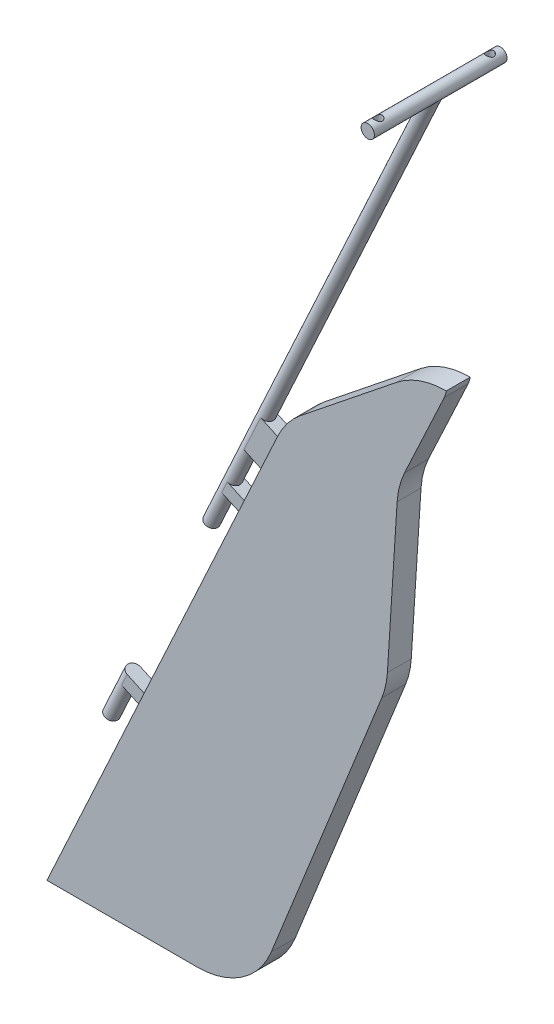
SolidWorks part; units mm, degrees
ref_plane "Plan de face" through (0, 0, 0) normal (0, 0, 1) x (1, 0, 0)
ref_plane "Plan de dessus" through (0, 0, 0) normal (0, 1, 0) x (1, 0, 0)
ref_plane "Plan de droite" through (0, 0, 0) normal (1, 0, 0) x (0, 0, -1)
sketch "Esquisse1" plane through (0, 0, 0) normal (0, 0, 1) x (1, 0, 0)
  line L0 (0, 0) -> (90, 195)
  line L1 (90, 195) -> (140, 235)
  line L3 (76.9505, 0) -> (0, 0)
  line L4 (140, 235) -> (150.9326, 235)
  line L5 (150.9326, 235) -> (132.3394, 195.2011)
  line L6 (132.3394, 195.2011) -> (127.9972, 127.139)
  line L7 (127.9972, 127.139) -> (76.9505, 0)
  dimension "D1" = 195
  dimension "D2" = 90
  dimension "D3" = 40
  dimension "D4" = 50
extrude "Boss.-Extru.1" add sketch "Esquisse1" along normal blind 9
sketch "Esquisse36" plane through (0, 0, 0) normal (-0.908, 0.4191, 0) x (0, 0, 1)
  line L0 (9, 214.7673) -> (9, 0) construction
  line L1 (7, 174.7673) -> (2, 174.7673)
  line L2 (7, 174.7673) -> (7, 169.7673)
  line L3 (7, 169.7673) -> (2, 169.7673)
  line L4 (2, 174.7673) -> (2, 169.7673)
  line L5 (7, 84.7673) -> (2, 84.7673)
  line L6 (7, 84.7673) -> (7, 79.7673)
  line L7 (7, 79.7673) -> (2, 79.7673)
  line L8 (2, 84.7673) -> (2, 79.7673)
  line L9 (9, 214.7673) -> (0, 214.7673) construction
  line L10 (7, 204.7673) -> (2, 204.7673)
  line L11 (7, 204.7673) -> (7, 189.7673)
  line L12 (7, 189.7673) -> (2, 189.7673)
  line L13 (2, 204.7673) -> (2, 189.7673)
  point P12 (4.5, 214.7673)
  dimension "D1" = 5
  dimension "D2" = 5
  dimension "D3" = 2
  dimension "D4" = 5
  dimension "D5" = 5
  dimension "D6" = 2
  dimension "D7" = 40
  dimension "D8" = 130
  dimension "D9" = 5
  dimension "D10" = 15
  dimension "D11" = 2
  dimension "D12" = 10
extrude "Boss.-Extru.4" add sketch "Esquisse36" along normal blind 8
sketch "Esquisse37" plane through (-7.2637, 3.3525, 0) normal (-0.908, 0.4191, 0) x (0, 0, 1)
  line L0 (4.5, 354.7673) -> (4.5, 154.7673)
  line L2 (2, 169.7673) -> (7, 169.7673) construction
  line L3 (7, 204.7673) -> (2, 204.7673) construction
  line L4 (7, 174.7673) -> (2, 174.7673) construction
  line L5 (7, 204.7673) -> (2, 204.7673) construction
  point P7 (4.5, 169.7673)
  point P10 (4.5, 204.7673)
  dimension "D1" = 20
  dimension "D2" = 150
sweep "Balayage2" add path "Esquisse37" circular profile diameter 5 parameters "D3"=5
sketch "Esquisse50" plane through (-7.2637, 3.3525, 0) normal (-0.908, 0.4191, 0) x (0, 0, 1)
  line L0 (4.5, 84.7673) -> (4.5, 64.7673)
  line L1 (7, 84.7673) -> (2, 84.7673) construction
  line L3 (2, 79.7673) -> (7, 79.7673) construction
  point P7 (4.5, 79.7673)
  dimension "D1" = 20
sweep "Balayage3" add path "Esquisse50" circular profile diameter 5 parameters "D3"=5
fillet "Congé2" radius 30 5 edges at (90, 195, 4.5) (140, 235, 4.5) (132.3394, 195.2011, 4.5) (127.9972, 127.139, 4.5) (76.9505, 0, 4.5)
fillet "Congé3" radius 10 1 edges at (150.9326, 235, 4.5)
sketch "Esquisse88" plane through (148.6681, 322.1143, 0) normal (0.4191, 0.908, 0) x (0.908, -0.4191, 0)
  line L0 (-8, 20.5) -> (-8, -29.5)
  circle A0 centre (-8, -4.5) radius 2.5 construction
  point P3 (-8, -4.5)
  dimension "D1" = 50
sweep "Balayage4" add path "Esquisse88" circular profile diameter 5 parameters "D3"=5
sketch "Esquisse103" plane through (0, 0, 0) normal (0, 1, 0) x (1, 0, 0)
  line L0 (141.4045, -29.5) -> (141.4045, 20.5) construction
  line L1 (138.9045, -29.5) -> (143.9045, -29.5) construction
  line L2 (143.9045, 20.5) -> (138.9045, 20.5) construction
  circle A0 centre (141.4045, 16.5) radius 1.5
  circle A1 centre (141.3919, -25.5) radius 1.5
  dimension "D1" = 3
  dimension "D3" = 3
  dimension "D2" = 4
  dimension "D4" = 4
extrude "Enlèv. mat.-Extru.2" cut sketch "Esquisse103" against normal blind 10 and the other way through all
